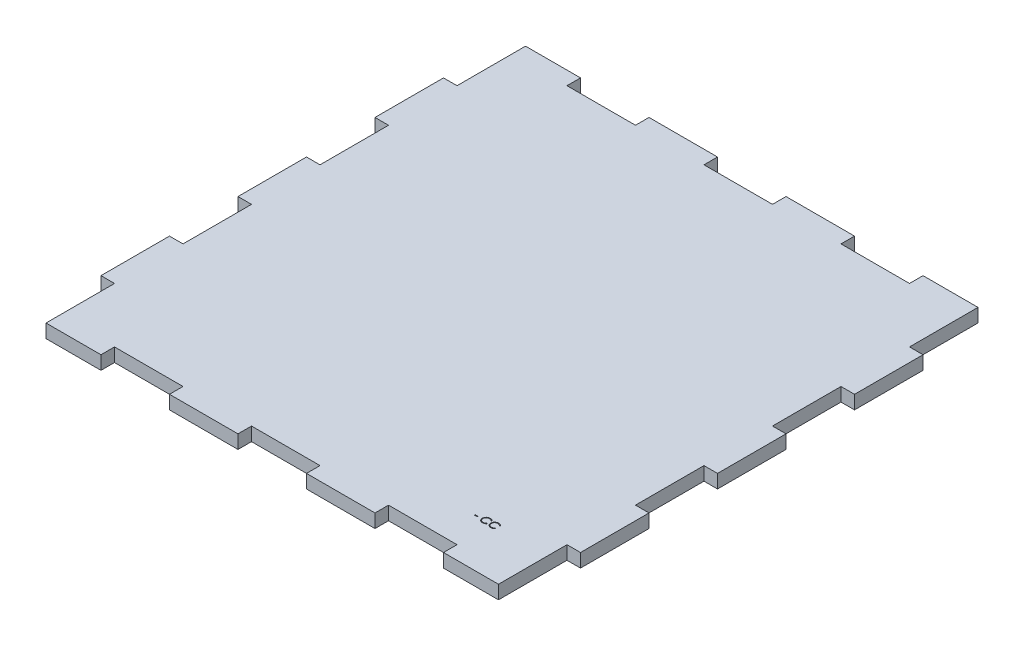
SolidWorks part; units mm, degrees
ref_plane "Front Plane" through (0, 0, 0) normal (0, 0, 1) x (1, 0, 0)
ref_plane "Top Plane" through (0, 0, 0) normal (0, 1, 0) x (1, 0, 0)
ref_plane "Right Plane" through (0, 0, 0) normal (1, 0, 0) x (0, 0, -1)
sketch "Sketch1" plane through (0, 0, 0) normal (0, 1, 0) x (1, 0, 0)
  line L48 (32.1429, 0) -> (32.1429, 6.35)
  line L49 (0, 0) -> (32.1429, 0)
  line L50 (0, 0) -> (0, 6.35)
  line L51 (0, 6.35) -> (32.1429, 6.35)
  line L52 (32.1429, 0) -> (32.1429, 6.35)
  line L53 (0, 0) -> (6.35, 0)
  line L54 (0, 0) -> (0, 32.1429)
  line L55 (0, 32.1429) -> (6.35, 32.1429)
  line L56 (6.35, 0) -> (6.35, 32.1429)
  line L57 (32.1429, 0) -> (64.2857, 0)
  line L58 (64.2857, 0) -> (64.2857, 6.35)
  line L59 (32.1429, 6.35) -> (64.2857, 6.35)
  line L60 (64.2857, 0) -> (64.2857, 6.35)
  line L61 (64.2857, 0) -> (96.4286, 0)
  line L62 (96.4286, 0) -> (96.4286, 6.35)
  line L63 (64.2857, 6.35) -> (96.4286, 6.35)
  line L64 (96.4286, 0) -> (96.4286, 6.35)
  line L65 (96.4286, 0) -> (128.5714, 0)
  line L66 (128.5714, 0) -> (128.5714, 6.35)
  line L67 (96.4286, 6.35) -> (128.5714, 6.35)
  line L72 (128.5714, 0) -> (128.5714, 6.35)
  line L73 (128.5714, 0) -> (160.7143, 0)
  line L74 (160.7143, 0) -> (160.7143, 6.35)
  line L75 (128.5714, 6.35) -> (160.7143, 6.35)
  line L76 (160.7143, 0) -> (160.7143, 6.35)
  line L77 (160.7143, 0) -> (192.8571, 0)
  line L78 (192.8571, 0) -> (192.8571, 6.35)
  line L79 (160.7143, 6.35) -> (192.8571, 6.35)
  line L80 (192.8571, 0) -> (192.8571, 6.35)
  line L81 (192.8571, 0) -> (225, 0)
  line L82 (225, 0) -> (225, 6.35)
  line L83 (192.8571, 6.35) -> (225, 6.35)
  line L84 (0, 32.1429) -> (0, 64.2857)
  line L85 (0, 32.1429) -> (6.35, 32.1429)
  line L86 (6.35, 32.1429) -> (6.35, 64.2857)
  line L87 (0, 64.2857) -> (6.35, 64.2857)
  line L88 (0, 64.2857) -> (0, 96.4286)
  line L89 (0, 64.2857) -> (6.35, 64.2857)
  line L90 (6.35, 64.2857) -> (6.35, 96.4286)
  line L91 (0, 96.4286) -> (6.35, 96.4286)
  line L98 (0, 96.4286) -> (0, 128.5714)
  line L99 (0, 96.4286) -> (6.35, 96.4286)
  line L100 (6.35, 96.4286) -> (6.35, 128.5714)
  line L101 (0, 128.5714) -> (6.35, 128.5714)
  line L102 (0, 128.5714) -> (0, 160.7143)
  line L103 (0, 128.5714) -> (6.35, 128.5714)
  line L104 (6.35, 128.5714) -> (6.35, 160.7143)
  line L105 (0, 160.7143) -> (6.35, 160.7143)
  line L106 (0, 160.7143) -> (0, 192.8571)
  line L107 (0, 160.7143) -> (6.35, 160.7143)
  line L108 (6.35, 160.7143) -> (6.35, 192.8571)
  line L109 (0, 192.8571) -> (6.35, 192.8571)
  line L110 (0, 192.8571) -> (0, 225)
  line L111 (0, 192.8571) -> (6.35, 192.8571)
  line L112 (6.35, 192.8571) -> (6.35, 225)
  line L113 (0, 225) -> (6.35, 225)
  line L114 (112.5, 0) -> (112.5, 671.069) construction
  line L115 (-187.856, 112.5) -> (254.8092, 112.5) construction
  line L116 (225, 32.1429) -> (218.65, 32.1429)
  line L117 (218.65, 0) -> (218.65, 32.1429)
  line L118 (225, 0) -> (218.65, 0)
  line L119 (225, 0) -> (225, 32.1429)
  line L120 (225, 192.8571) -> (218.65, 192.8571)
  line L121 (218.65, 192.8571) -> (218.65, 225)
  line L122 (225, 225) -> (218.65, 225)
  line L123 (225, 192.8571) -> (225, 225)
  line L124 (225, 160.7143) -> (218.65, 160.7143)
  line L125 (218.65, 160.7143) -> (218.65, 192.8571)
  line L126 (225, 192.8571) -> (218.65, 192.8571)
  line L127 (225, 160.7143) -> (225, 192.8571)
  line L128 (225, 32.1429) -> (218.65, 32.1429)
  line L129 (218.65, 32.1429) -> (218.65, 64.2857)
  line L130 (225, 64.2857) -> (218.65, 64.2857)
  line L131 (225, 32.1429) -> (225, 64.2857)
  line L132 (225, 128.5714) -> (218.65, 128.5714)
  line L133 (218.65, 128.5714) -> (218.65, 160.7143)
  line L134 (225, 160.7143) -> (218.65, 160.7143)
  line L135 (225, 128.5714) -> (225, 160.7143)
  line L136 (225, 96.4286) -> (218.65, 96.4286)
  line L137 (218.65, 96.4286) -> (218.65, 128.5714)
  line L138 (225, 128.5714) -> (218.65, 128.5714)
  line L139 (225, 96.4286) -> (225, 128.5714)
  line L140 (225, 64.2857) -> (218.65, 64.2857)
  line L141 (218.65, 64.2857) -> (218.65, 96.4286)
  line L142 (225, 96.4286) -> (218.65, 96.4286)
  line L143 (225, 64.2857) -> (225, 96.4286)
  line L144 (192.8571, 225) -> (225, 225)
  line L145 (225, 225) -> (225, 218.65)
  line L146 (192.8571, 218.65) -> (225, 218.65)
  line L147 (192.8571, 225) -> (192.8571, 218.65)
  line L148 (160.7143, 225) -> (192.8571, 225)
  line L149 (192.8571, 225) -> (192.8571, 218.65)
  line L150 (160.7143, 218.65) -> (192.8571, 218.65)
  line L151 (160.7143, 225) -> (160.7143, 218.65)
  line L152 (128.5714, 225) -> (160.7143, 225)
  line L153 (160.7143, 225) -> (160.7143, 218.65)
  line L154 (128.5714, 218.65) -> (160.7143, 218.65)
  line L155 (128.5714, 225) -> (128.5714, 218.65)
  line L156 (96.4286, 225) -> (128.5714, 225)
  line L157 (128.5714, 225) -> (128.5714, 218.65)
  line L158 (96.4286, 218.65) -> (128.5714, 218.65)
  line L159 (96.4286, 225) -> (96.4286, 218.65)
  line L160 (64.2857, 225) -> (96.4286, 225)
  line L161 (96.4286, 225) -> (96.4286, 218.65)
  line L162 (64.2857, 218.65) -> (96.4286, 218.65)
  line L163 (64.2857, 225) -> (64.2857, 218.65)
  line L164 (32.1429, 225) -> (64.2857, 225)
  line L165 (64.2857, 225) -> (64.2857, 218.65)
  line L166 (32.1429, 218.65) -> (64.2857, 218.65)
  line L167 (32.1429, 225) -> (32.1429, 218.65)
  line L168 (0, 218.65) -> (32.1429, 218.65)
  line L169 (32.1429, 225) -> (32.1429, 218.65)
  line L170 (0, 225) -> (32.1429, 225)
  line L171 (0, 225) -> (0, 218.65)
  point P56 (112.5, 6.35)
  point P58 (6.35, 112.5)
  dimension "D3" = 225
  dimension "D4" = 225
  dimension "D5" = 6.35
  dimension "D2" = 7
  dimension "D1" = 7
extrude "Boss-Extrude1" add sketch "Sketch1" along normal blind 6.35 contours L168 L112 L108 L104 L100 L90 L86 L56 L51 L59 L63 L67 L75 L79 L83 L117 L129 L141 L137 L133 L125 L121 L146 L150 L154 L158 L162 L166 | L101 L98 L91 L100 | L87 L84 L55 L86 | L109 L106 L105 L108 | L56 L49 L48 L51 | L63 L58 L61 L62 | L75 L66 L73 L74 | L81 L117 L83 L78 | L116 L131 L130 L129 | L136 L139 L132 L137 | L124 L127 L120 L125 | L144 L147 L146 L121 | L152 L155 L154 L151 | L160 L163 L162 L159 | L170 L112 L168 L167 region at (19.2464, 0, -3.175) region at (112.5, 0, -112.5) region at (80.3571, 0, -3.175) region at (3.175, 0, -48.2143) region at (144.6429, 0, -3.175) region at (3.175, 0, -112.5) region at (205.7536, 0, -3.175) region at (3.175, 0, -176.7857) region at (221.825, 0, -48.2143) region at (19.2464, 0, -221.825) region at (221.825, 0, -112.5) region at (80.3571, 0, -221.825) region at (221.825, 0, -176.7857) region at (144.6429, 0, -221.825) region at (205.7536, 0, -221.825)
sketch "Sketch2" plane through (0, 6.35, 0) normal (0, 1, 0) x (1, 0, 0)
  text T0 "- CC"
  point P1 (40.6439, 103.5462)
  point P2 (184.7947, 21.2852)
extrude "Cut-Extrude1" cut sketch "Sketch2" against normal through all
